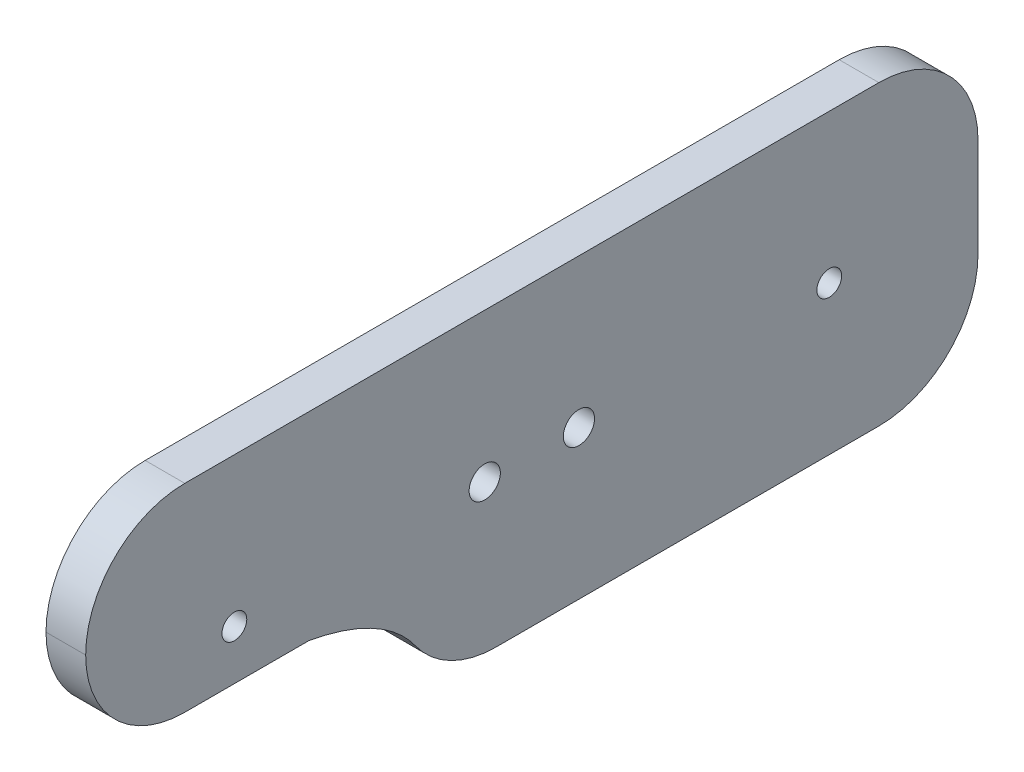
SolidWorks part; units mm, degrees
material "Du"
ref_plane "Front Plane" through (0, 0, 0) normal (0, 0, 1) x (1, 0, 0)
ref_plane "Top Plane" through (0, 0, 0) normal (0, 1, 0) x (1, 0, 0)
ref_plane "Right Plane" through (0, 0, 0) normal (1, 0, 0) x (0, 0, -1)
sketch "Sketch1" plane through (0, 0, 0) normal (1, 0, 0) x (0, 0, -1)
  line L1 (-45, -15) -> (45, -15)
  line L2 (-45, -15) -> (-45, 15)
  line L3 (-45, 15) -> (45, 15)
  line L4 (45, -15) -> (45, 15)
  line L5 (-45, -15) -> (45, 15) construction
  line L6 (-45, 15) -> (45, -15) construction
  point P0 (0, 0)
  dimension "D1" = 90
  dimension "D2" = 30
extrude "Boss-Extrude1" add sketch "Sketch1" along normal blind 4
sketch "Sketch6" plane through (4, 0, 0) normal (1, 0, 0) x (0, 0, -1)
  line L0 (2.2, 0) -> (-2.2, 0) construction
  circle A0 centre (-4.75, 0) radius 1.575
  dimension "D1" = 3.15
  dimension "D2" = 4.75
extrude "Cut-Extrude6" cut sketch "Sketch6" against normal through all
sketch "Sketch7" plane through (4, 0, 0) normal (1, 0, 0) x (0, 0, -1)
  line L0 (2.2, 0) -> (-2.2, 0) construction
  circle A0 centre (4.75, 0) radius 1.575
  dimension "D1" = 3.15
  dimension "D2" = 4.75
extrude "Cut-Extrude7" cut sketch "Sketch7" against normal through all
sketch "Sketch13" plane through (4, 0, 0) normal (1, 0, 0) x (0, 0, -1)
  line L0 (2.2, 0) -> (-2.2, 0) construction
  line L1 (-45, 15) -> (-45, -15) construction
  circle A0 centre (-30, 0) radius 1.25
  dimension "D1" = 2.5
  dimension "D2" = 15
extrude "Cut-Extrude13" cut sketch "Sketch13" against normal through all
sketch "Sketch14" plane through (4, 0, 0) normal (1, 0, 0) x (0, 0, -1)
  line L0 (2.2, 0) -> (-2.2, 0) construction
  line L1 (45, -15) -> (45, 15) construction
  circle A0 centre (30, 0) radius 1.25
  dimension "D1" = 2.5
  dimension "D2" = 15
extrude "Cut-Extrude14" cut sketch "Sketch14" against normal through all
sketch "Sketch15" plane through (4, 0, 0) normal (1, 0, 0) x (0, 0, -1)
  line L1 (-45, -15) -> (-30, -15)
  line L2 (-45, -15) -> (-45, -5)
  line L3 (-45, -5) -> (-30, -5)
  line L4 (-30, -15) -> (-30, -5)
  dimension "D1" = 15
  dimension "D2" = 10
extrude "Cut-Extrude15" cut sketch "Sketch15" against normal through all
fillet "Fillet1" radius 10 3 edges at (2, -15, -45) (2, 15, -45) (2, 15, 45)
sketch "Sketch16" plane through (4, 0, 0) normal (1, 0, 0) x (0, 0, -1)
  line L1 (-30, -5) -> (-10, -5)
  line L3 (-10, -5) -> (-10, -15)
  line L6 (-30, -15) -> (35, -15) construction
  line L7 (-10, -15) -> (-30, -15)
  line L8 (-30, -15) -> (-30, -5)
  dimension "D1" = 20
extrude "Cut-Extrude16" cut sketch "Sketch16" against normal through all
fillet "Fillet2" radius 10 1 edges at (2, -5, 45)
sketch "Sketch17" plane through (4, 0, 0) normal (1, 0, 0) x (0, 0, -1)
  line L0 (-10, -5) -> (-35, -5) construction
  line L1 (-43.4014, -1.3145) -> (-1.5986, -8.6855) construction
  line L2 (-10, -15) -> (-10, -5) construction
  line L3 (-12.7797, 0.7646) -> (-7.2203, -30.7646) construction
  line L4 (-22.5, -5) -> (-10, -5)
  line L5 (-10, -5) -> (-10, -15)
  spline S0 degree 3 poles (-10, -15) (-10.9266, -9.7451) (-15.5329, -6.2285) (-22.5, -5) knots 0 0 0 0 1 1 1 1
  dimension "D1" = 10
  dimension "D2" = 10
extrude "Boss-Extrude2" add sketch "Sketch17" against normal blind 4
fillet "Fillet3" radius 10 1 edges at (2, -15, 10)
